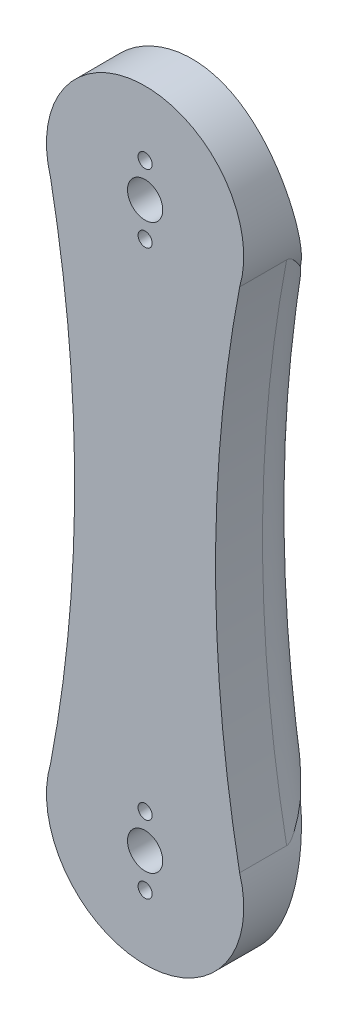
SolidWorks part; units mm, degrees
ref_plane "Front Plane" through (0, 0, 0) normal (0, 0, 1) x (1, 0, 0)
ref_plane "Top Plane" through (0, 0, 0) normal (0, 1, 0) x (1, 0, 0)
ref_plane "Right Plane" through (0, 0, 0) normal (1, 0, 0) x (0, 0, -1)
sketch "Sketch1" plane through (0, 0, 0) normal (0, 0, 1) x (1, 0, 0)
  line L0 (0, 120) -> (0, 0) construction
  circle A0 centre (0, 0) radius 21
  circle A1 centre (0, 120) radius 21
  arc A2 (-20.1246, 114) -> (-20.1246, 6) centre (-302.0717, 60) cw
  arc A3 (20.1246, 114) -> (20.1246, 6) centre (302.0717, 60) ccw
  point P8 (-15, 60)
  dimension "D1" = 42
  dimension "D2" = 42
  dimension "D3" = 120
  dimension "D4" = 15
  dimension "D5" = 6
  dimension "D6" = 6
extrude "Boss-Extrude1" add sketch "Sketch1" against normal blind 21 contours A1 L0 A0 A3 | L0 A1 A2 A0 | A0 | A1 region at (8.524, 60, 0) region at (-8.524, 60, 0) region at (12.1949, 16.3612, 0)
sketch "Sketch2" plane through (0, 0, 0) normal (1, 0, 0) x (0, 0, -1)
  line L0 (21, 141) -> (21, 99)
  line L1 (21, 114) -> (21, 141) construction
  line L2 (21, 141) -> (10, 141)
  line L3 (21, 60) -> (86.6031, 60) construction
  line L4 (21, 6) -> (21, 114) construction
  line L5 (21, -21) -> (10, -21)
  line L6 (21, -21) -> (21, 21)
  arc A0 (10, 141) -> (21, 99) centre (69.6102, 134.1717) ccw
  arc A1 (10, -21) -> (21, 21) centre (69.6102, -14.1717) cw
  dimension "D3" = 60
  dimension "D1" = 11
  dimension "D2" = 42
extrude "Cut-Extrude1" cut sketch "Sketch2" against normal through all both and the other way through all
fillet "Fillet1" radius 11 2 edges at (-15, 60, -21) (15, 60, -21)
sketch "Sketch3" plane through (0, 0, 0) normal (0, 1, 0) x (1, 0, 0)
  line L0 (-6.5624, 21) -> (6.5624, 21) construction
  circle A0 centre (0, 12) radius 5.75
  dimension "D1" = 11.5
  dimension "D2" = 9
extrude "Cut-Extrude2" cut sketch "Sketch3" along normal blind 125
sketch "Sketch6" plane through (0, 0, 0) normal (0, 0, 1) x (1, 0, 0)
  line L0 (15, 60) -> (83.089, 60) construction
  circle A0 centre (0, 120) radius 18
  arc A1 (20.1246, 114) -> (20.1246, 6) centre (302.0717, 60) ccw construction
  circle A2 centre (0, 0) radius 18
  arc A3 (17.2497, 114.8571) -> (-17.2497, 114.8571) centre (0, 120) ccw
  arc A4 (17.2497, 114.8571) -> (-17.2497, 114.8571) centre (0, 120) ccw
  dimension "D1" = 3
extrude "Cut-Extrude3" cut sketch "Sketch6" against normal blind 125 from offset 6 contours A0 | A2 offset against normal yes
sketch "Sketch7" plane through (0, 0, -6) normal (0, 0, -1) x (-1, 0, 0)
  line L0 (4, 60) -> (-68.5347, 60) construction
  circle A0 centre (0, 0) radius 3.75
  circle A1 centre (0, 7.25) radius 1.5
  circle A2 centre (0, -7.25) radius 1.5
  arc A3 (6.5624, 99) -> (6.5624, 21) centre (302.0717, 60) ccw construction
  circle A4 centre (0, 127.25) radius 1.5
  circle A5 centre (0, 112.75) radius 1.5
  circle A6 centre (0, 120) radius 3.75
  dimension "D1" = 7.25
  dimension "D2" = 7.25
  dimension "D3" = 3
  dimension "D4" = 7.5
extrude "Cut-Extrude4" cut sketch "Sketch7" against normal blind 125
